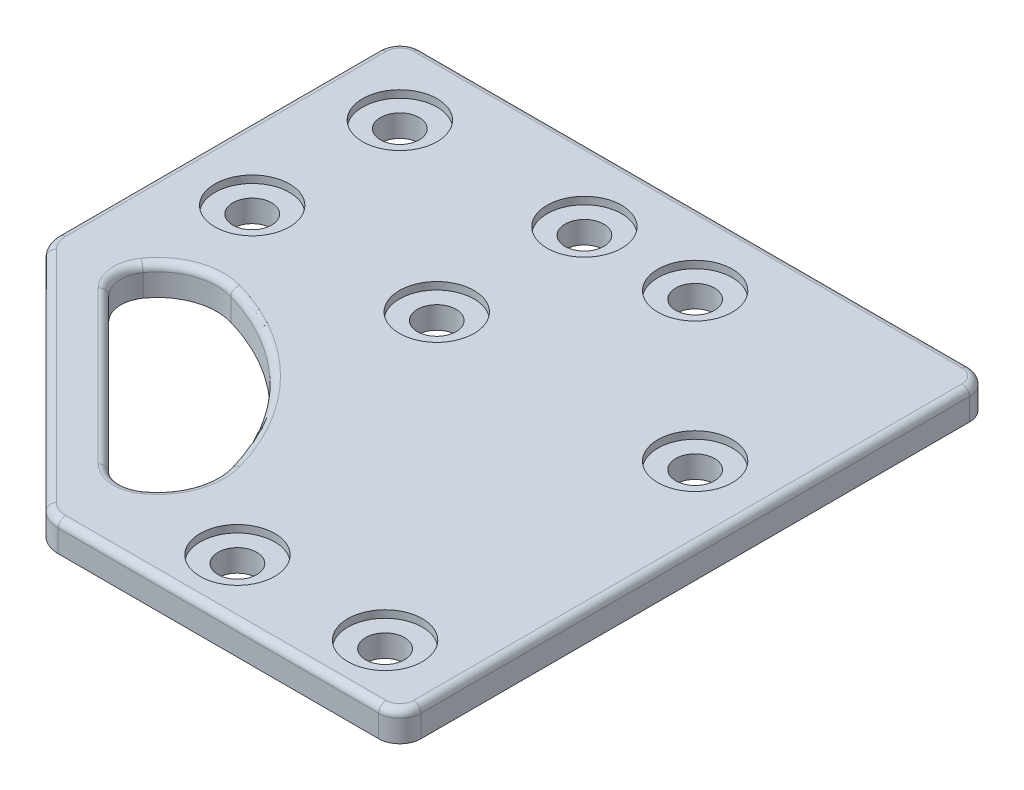
SolidWorks part; units mm, degrees
ref_plane "Front Plane" through (0, 0, 0) normal (0, 0, 1) x (1, 0, 0)
ref_plane "Top Plane" through (0, 0, 0) normal (0, 1, 0) x (1, 0, 0)
ref_plane "Right Plane" through (0, 0, 0) normal (1, 0, 0) x (0, 0, -1)
sketch "Sketch1" plane through (0, 0, 0) normal (0, 1, 0) x (1, 0, 0)
  line L0 (-70, -10) -> (-45, -10) construction
  line L1 (-2.8633, 0) -> (-77.1367, 0)
  line L2 (0, -2.8633) -> (0, -77.1367)
  line L3 (-2.8633, -80) -> (-37.1367, -80)
  line L4 (-80, -2.8633) -> (-80, -37.1367)
  line L5 (-70, -30) -> (-45, -30) construction
  line L6 (-10, -30) -> (-10, -72) construction
  line L7 (-30, -10) -> (-30, -72) construction
  line L8 (-71.8429, -40) -> (-40, -40)
  line L9 (-40, -40) -> (-40, -71.8429)
  line L10 (-80, -37.1367) -> (-80, -47.929)
  line L11 (-80, -47.929) -> (-47.929, -80)
  line L12 (-47.929, -80) -> (-37.1367, -80)
  line L13 (-40, -71.8429) -> (-47.6008, -71.8429)
  line L14 (-47.6008, -71.8429) -> (-71.8429, -47.6008)
  line L15 (-71.8429, -47.6008) -> (-71.8429, -40)
  circle A0 centre (-70, -10) radius 2.625
  circle A1 centre (-45, -10) radius 2.625
  circle A2 centre (-45, -30) radius 2.625
  circle A3 centre (-70, -30) radius 2.625
  circle A4 centre (-30, -10) radius 2.625
  circle A5 centre (-10, -30) radius 2.625
  circle A6 centre (-10, -72) radius 2.625
  circle A7 centre (-30, -72) radius 2.625
  arc A9 (-2.8633, -80) -> (0, -77.1367) centre (-2.8633, -77.1367) ccw
  arc A10 (0, -2.8633) -> (-2.8633, 0) centre (-2.8633, -2.8633) ccw
  arc A11 (-77.1367, 0) -> (-80, -2.8633) centre (-77.1367, -2.8633) ccw
  point P24 (-40, -80)
  point P29 (0, -80)
  point P32 (0, 0)
  point P35 (-80, 0)
  dimension "D2" = 5.25
  dimension "D3" = 10
  dimension "D4" = 20
  dimension "D5" = 10
  dimension "D6" = 20
  dimension "D7" = 8
  dimension "D8" = 10
  dimension "D9" = 50
  dimension "D10" = 35
  dimension "D11" = 80
  dimension "D12" = 80
  dimension "D13" = 15
  dimension "D14" = 40
  dimension "D15" = 40
  dimension "D17" = 42
  dimension "D18" = 6
extrude "Boss-Extrude1" add sketch "Sketch1" along normal blind 4
fillet "Fillet1" radius 30 1 edges at (-40, 2, 40)
sketch "Sketch2" plane through (0, 0, 0) normal (0, -1, 0) x (1, 0, 0)
  circle A0 centre (-10, 30) radius 5.05
  circle A1 centre (-30, 10) radius 5.05
  circle A2 centre (-45, 10) radius 5.05
  circle A3 centre (-70, 10) radius 5.05
  circle A4 centre (-70, 30) radius 5.05
  circle A5 centre (-45, 30) radius 5.05
  circle A6 centre (-30, 72) radius 5.05
  circle A7 centre (-10, 72) radius 5.05
  circle A8 centre (-45, 30) radius 2.625 construction
  dimension "D1" = 10.1
extrude "Cut-Extrude1" cut sketch "Sketch2" along normal blind 1 from surface starting at face at (-10, 4, 74.625)
fillet "Fillet2" [suppressed] radius 1
fillet "Fillet3" radius 1 7 edges at (-0.8386, 4, 0.8386) (0, 4, 40) (-0.8386, 4, 79.1614) (-25.3961, 4, 80) (-80, 4, 25.3961) (-79.1614, 4, 0.8386) (-40, 4, 0)
fillet "Fillet4" radius 8 2 edges at (-40, 2, 71.8429) (-71.8429, 2, 40)
fillet "Fillet5" radius 4 2 edges at (-47.6008, 2, 71.8429) (-71.8429, 2, 47.6008)
fillet "Fillet6" radius 4 2 edges at (-47.929, 1.5, 80) (-80, 1.5, 47.929) tangent propagation no
fillet "Fillet7" radius 1 9 edges at (-78.9156, 4, 49.0106) (-49.0106, 4, 78.9156) (-63.9645, 4, 63.9645) (-66.6211, 4, 41.313) (-71.2074, 4, 46.9171) (-59.7219, 4, 59.7219) (-46.9171, 4, 71.2074) (-41.313, 4, 66.6211) (-48.7868, 4, 48.7868)
